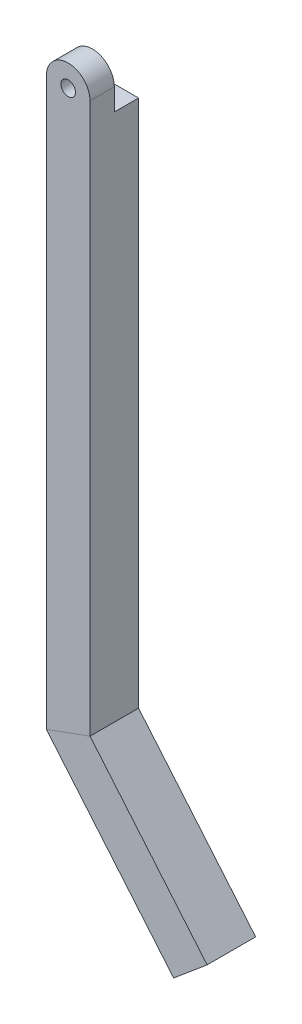
SolidWorks part; units mm, degrees
ref_plane "前视基准面" through (0, 0, 0) normal (0, 0, 1) x (1, 0, 0)
ref_plane "上视基准面" through (0, 0, 0) normal (0, 1, 0) x (1, 0, 0)
ref_plane "右视基准面" through (0, 0, 0) normal (1, 0, 0) x (0, 0, -1)
sketch "草图4" plane through (0, 0, 0) normal (0, 1, 0) x (1, 0, 0)
  line L0 (-24.3, 1.0429) -> (-15.3, 1.0429)
  line L1 (-15.3, 1.0429) -> (-15.3, -8.9571)
  line L2 (-15.3, -8.9571) -> (-24.3, -8.9571)
  line L3 (-24.3, -8.9571) -> (-24.3, 1.0429)
  line L4 (-24.3, 1.0429) -> (-15.3, -8.9571) construction
  line L5 (-15.3, 1.0429) -> (-24.3, -8.9571) construction
  point P3 (-19.8, -3.9571)
  dimension "D1" = 9
  dimension "D2" = 10
extrude "凸台-拉伸2" add sketch "草图4" along normal blind 10
ref_plane "镜腿扫描轨迹基准面" through (0, 0, 3.9571) normal (0, 0, 1) x (1, 0, 0)
sketch "草图5" plane through (0, 0, 3.9571) normal (0, 0, 1) x (1, 0, 0)
  line L0 (-19.8, 0) -> (-19.8, -110)
  line L1 (-24.3, 0) -> (-15.3, 0) construction
  line L2 (-19.8, -110) -> (5.373, -140)
  dimension "D1" = 110
  dimension "D2" = 30
  dimension "D3" = 140
sketch "草图6" plane through (0, 0, 8.9571) normal (0, 0, 1) x (1, 0, 0)
  line L0 (-24.3, 10) -> (-24.3, 5)
  line L1 (-24.3, 10) -> (-24.3, 0) construction
  line L2 (-24.3, 10) -> (-15.3, 10)
  line L3 (-15.3, 10) -> (-15.3, 5)
  line L4 (-15.3, 10) -> (-15.3, 0) construction
  arc A0 (-24.3, 5) -> (-15.3, 5) centre (-19.8, 5) cw
  dimension "D1" = 5
  dimension "D2" = 5
extrude "切除-拉伸1" cut sketch "草图6" against normal blind 10
sweep "扫描2" add profiles "草图4<2>" path "草图5"
sketch "草图4<2>" plane through (0, 0, 0) normal (0, 1, 0) x (1, 0, 0) same geometry as "草图4"
ref_plane "connection口生成草图基准面" through (0, 0, 3.9571) normal (0, 0, 1) x (1, 0, 0)
sketch "草图7" plane through (0, 0, 3.9571) normal (0, 0, 1) x (1, 0, 0)
  line L0 (-24.3, 5) -> (-24.3, 0.5)
  line L1 (-24.3, 5) -> (-24.3, -111.6379) construction
  line L2 (-24.3, 0.5) -> (-15.3, 0.5)
  line L3 (-15.3, 5) -> (-15.3, -108.3621) construction
  line L4 (-15.3, 0.5) -> (-15.3, 5)
  arc A0 (-24.3, 5) -> (-15.3, 5) centre (-19.8, 5) cw
  dimension "D1" = 4.5
extrude "切除-拉伸2" cut sketch "草图7" against normal blind 10
sketch "草图8" plane through (0, 0, 3.9571) normal (0, 0, -1) x (-1, 0, 0)
  line L3 (15.3, 5) -> (15.3, 0.5)
  line L4 (15.3, 0.5) -> (24.3, 0.5)
  line L5 (24.3, 0.5) -> (24.3, 5)
  line L6 (15.3, 5) -> (15.3, 0.5)
  line L7 (15.3, 0.5) -> (24.3, 0.5)
  line L8 (24.3, 0.5) -> (24.3, 5)
  circle A0 centre (19.8, 5) radius 1.5
  arc A1 (24.3, 5) -> (15.3, 5) centre (19.8, 5) ccw
  arc A2 (24.3, 5) -> (15.3, 5) centre (19.8, 5) ccw
  dimension "D2" = 3
  dimension "D1" = 0
extrude "切除-拉伸3" cut sketch "草图8" against normal blind 10 contours A0
